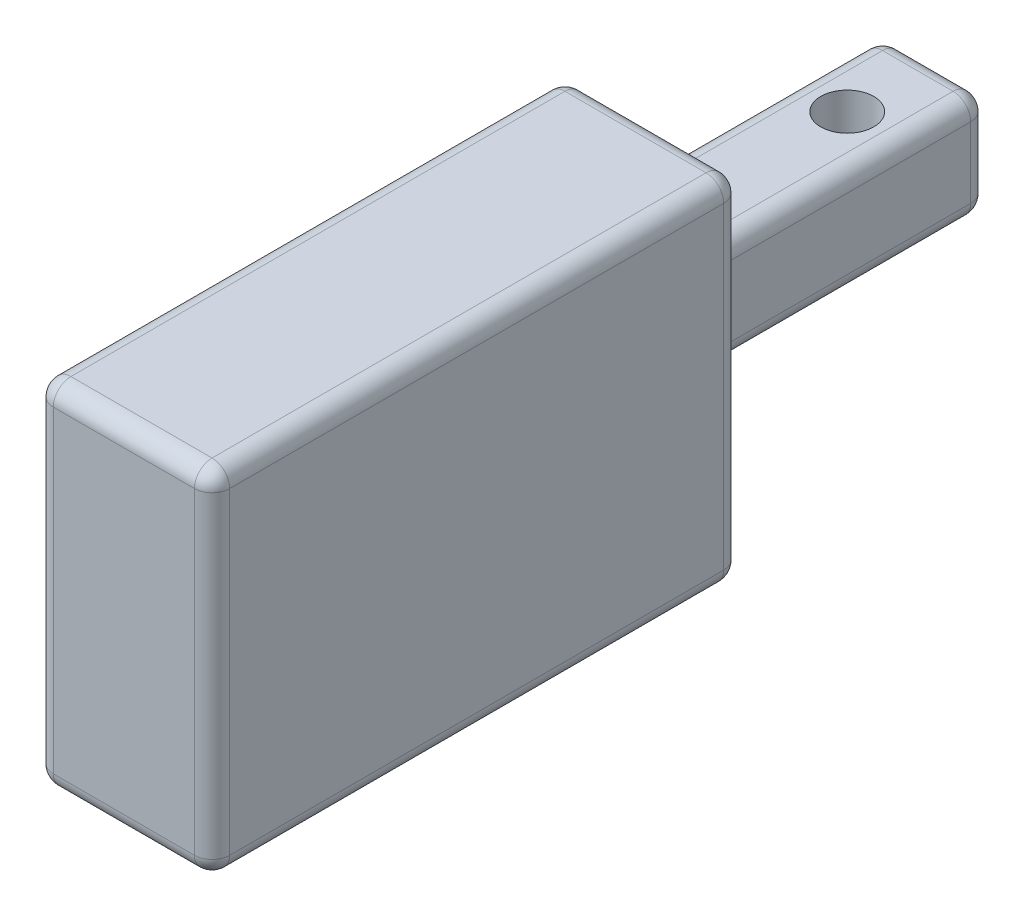
SolidWorks part; units mm, degrees
ref_plane "Front Plane" through (0, 0, 0) normal (0, 0, 1) x (1, 0, 0)
ref_plane "Top Plane" through (0, 0, 0) normal (0, 1, 0) x (1, 0, 0)
ref_plane "Right Plane" through (0, 0, 0) normal (1, 0, 0) x (0, 0, -1)
sketch "草图1" plane through (0, 0, 0) normal (0, 0, 1) x (1, 0, 0)
  line L1 (0, 0) -> (10, 0)
  line L2 (0, 0) -> (0, 22)
  line L3 (0, 22) -> (10, 22)
  line L4 (10, 0) -> (10, 22)
extrude "凸台-拉伸1" add sketch "草图1" along normal blind 30
sketch "草图2" plane through (0, 0, 0) normal (0, 0, 1) x (1, 0, 0)
  line L1 (2, 15) -> (8, 15)
  line L2 (2, 15) -> (2, 9)
  line L3 (2, 9) -> (8, 9)
  line L4 (8, 15) -> (8, 9)
extrude "凸台-拉伸3" add sketch "草图2" against normal blind 14
sketch "草图3" plane through (0, 9, 0) normal (0, -1, 0) x (-1, 0, 0)
  circle A0 centre (-5, 11) radius 1.5
extrude "切除-拉伸1" cut sketch "草图3" against normal blind 6
sketch "草图6" plane through (0, 22, 0) normal (0, 1, 0) x (1, 0, 0)
  line L1 (0, 0) -> (10, 0)
  line L2 (0, 0) -> (0, -30)
  line L3 (0, -30) -> (10, -30)
  line L4 (10, 0) -> (10, -30)
extrude "切除-拉伸2" cut sketch "草图6" against normal blind 2
sketch "草图7" plane through (0, 0, -14) normal (0, 0, -1) x (-1, 0, 0)
  line L1 (-2, 15) -> (-8, 15)
  line L2 (-2, 15) -> (-2, 9)
  line L3 (-2, 9) -> (-8, 9)
  line L4 (-8, 15) -> (-8, 9)
extrude "凸台-拉伸4" add sketch "草图7" along normal blind 2
sketch "草图8" plane through (0, 0, -16) normal (0, 0, -1) x (-1, 0, 0)
  circle A0 centre (-5, 12) radius 1
extrude "切除-拉伸3" cut sketch "草图8" against normal blind 4
fillet "圆角1" radius 1 24 edges at (5, 0, 30) (5, 20, 30) (10, 0, 15) (10, 10, 30) (10, 20, 15) (0, 10, 30) (0, 0, 15) (0, 20, 15) (2, 9, -8) (2, 12, -16) (2, 15, -8) (8, 15, -8) (8, 12, -16) (8, 9, -8) (8, 12, 0) (5, 9, 0) (2, 12, 0) (5, 15, 0) (0, 10, 0) (5, 0, 0) (10, 10, 0) (5, 20, 0) (5, 15, -16) (5, 9, -16)
